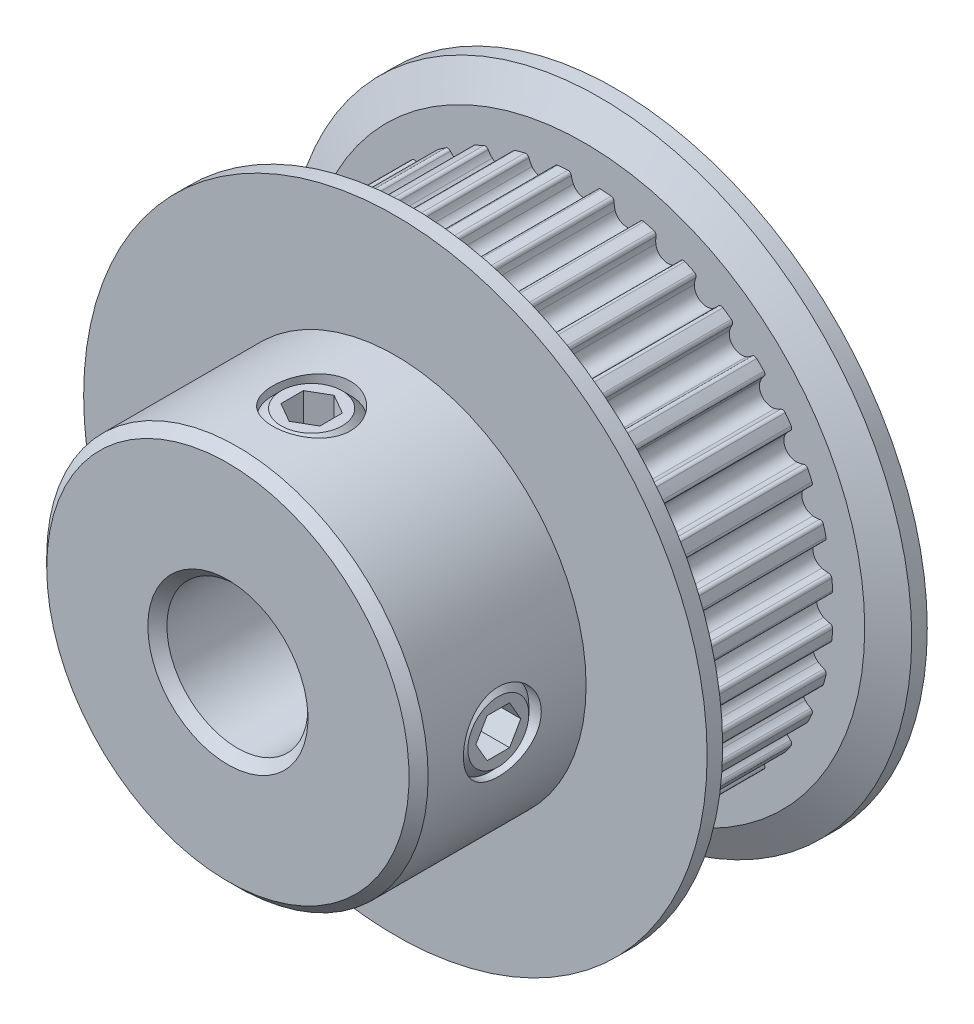
SolidWorks part; units mm, degrees
ref_plane "Front Plane" through (0, 0, 0) normal (0, 0, 1) x (1, 0, 0)
ref_plane "Top Plane" through (0, 0, 0) normal (0, 1, 0) x (1, 0, 0)
ref_plane "Right Plane" through (0, 0, 0) normal (1, 0, 0) x (0, 0, -1)
sketch "Sketch1" plane through (0, 0, 0) normal (0, 0, 1) x (1, 0, 0)
  line L1 (-1.8459, 10.4515) -> (1.8459, 10.4515) construction
  line L4 (0, 0) -> (0, 10.4515) construction
  line L5 (0, 10.4515) -> (0, 14.6063) construction
  line L6 (0, 11.4555) -> (1.9924, 11.2809) construction
  line L7 (1.9924, 11.2809) -> (2.8218, 11.1344) construction
  line L8 (1.9924, 11.2809) -> (1.8459, 10.4515) construction
  line L9 (-1.9924, 11.2809) -> (-1.8459, 10.4515) construction
  line L10 (-1.9482, 11.0308) -> (-2.4785, 14.0335)
  line L11 (-2.4785, 14.0335) -> (2.4785, 14.0335)
  line L12 (2.4785, 14.0335) -> (1.9482, 11.0308)
  circle A0 centre (0, 0) radius 11.4555 construction
  circle A1 centre (0, 0) radius 14.0335 construction
  circle A2 centre (0, 0) radius 11.2015 construction
  arc A3 (-0.4989, 10.7633) -> (0.4989, 10.7633) centre (0, 11.0065) ccw
  arc A4 (-0.4989, 10.7633) -> (-0.5884, 11.0497) centre (0.4, 11.2015) cw
  arc A5 (-1.9482, 11.0308) -> (-0.7467, 11.1766) centre (0, 0) cw
  arc A6 (-0.5884, 11.0497) -> (-0.7467, 11.1766) centre (-0.7367, 11.0269) ccw
  arc A7 (1.9482, 11.0308) -> (0.7467, 11.1766) centre (0, 0) ccw
  arc A8 (0.5884, 11.0497) -> (0.7467, 11.1766) centre (0.7367, 11.0269) cw
  arc A9 (0.4989, 10.7633) -> (0.5884, 11.0497) centre (-0.4, 11.2015) ccw
  point P6 (0, 20.9083)
  point P11 (0, 11.4555)
  point P13 (0, 14.0335)
  point P14 (0, 11.2015)
  dimension "D1" = 6.302
  dimension "D2" = 3.1508
sketch "Sketch2" plane through (0, 0, 0) normal (1, 0, 0) x (0, 0, -1)
  line L0 (-8.7249, 3.175) -> (8.7249, 3.175)
  line L1 (-8.7249, 3.175) -> (-8.7249, 8.585)
  line L2 (-8.7249, 8.585) -> (-1.1851, 8.585)
  line L3 (-1.1851, 8.585) -> (-1.1851, 14.0335)
  line L4 (-1.1851, 14.0335) -> (0.2149, 14.0335) construction
  line L5 (0.2149, 14.0335) -> (0.2149, 11.2015) construction
  line L6 (0.2149, 11.2015) -> (7.3249, 11.2015)
  line L7 (7.3249, 11.2015) -> (7.3249, 14.0335) construction
  line L8 (7.3249, 14.0335) -> (8.7249, 14.0335) construction
  line L9 (8.7249, 14.0335) -> (8.7249, 3.175)
  line L10 (-8.7249, 0) -> (8.7249, 0) construction
  line L11 (8.0249, 14.0335) -> (7.3249, 12.6175)
  line L12 (0.2149, 12.6175) -> (-0.4851, 14.0335)
  line L13 (-1.1851, 14.0335) -> (-0.4851, 14.0335)
  line L14 (0.2149, 12.6175) -> (0.2149, 11.2015)
  line L15 (7.3249, 11.2015) -> (7.3249, 12.6175)
  line L16 (8.0249, 14.0335) -> (8.7249, 14.0335)
  arc A0 (0.2149, 12.6175) -> (-0.4851, 14.0335) centre (-1.5673, 12.6175) ccw construction
  arc A1 (7.3249, 12.6175) -> (8.0249, 14.0335) centre (9.1071, 12.6175) cw construction
  point P12 (0.2149, 12.6175)
  point P14 (-0.4851, 14.0335)
  point P20 (7.3249, 12.6175)
  point P21 (8.0249, 14.0335)
  point P25 (7.3249, 0)
  point P26 (0.2149, 0)
revolve "Revolve1" add sketch "Sketch2" angle 360 mid plane about L10
sketch "Sketch3" plane through (0, 0, 0) normal (0, 0, 1) x (1, 0, 0)
  line L6 (2.4785, 14.0335) -> (-2.4785, 14.0335)
  line L7 (1.9482, 11.0308) -> (2.4785, 14.0335)
  line L8 (-2.4785, 14.0335) -> (-1.9482, 11.0308)
  line L9 (2.4785, 14.0335) -> (-2.4785, 14.0335)
  line L10 (1.9482, 11.0308) -> (2.4785, 14.0335)
  line L11 (-2.4785, 14.0335) -> (-1.9482, 11.0308)
  arc A8 (1.9482, 11.0308) -> (0.7467, 11.1766) centre (0, 0) ccw
  arc A9 (0.7467, 11.1766) -> (0.5884, 11.0497) centre (0.7367, 11.0269) ccw
  arc A10 (0.4989, 10.7633) -> (0.5884, 11.0497) centre (-0.4, 11.2015) ccw
  arc A11 (-0.4989, 10.7633) -> (0.4989, 10.7633) centre (0, 11.0065) ccw
  arc A12 (-0.5884, 11.0497) -> (-0.4989, 10.7633) centre (0.4, 11.2015) ccw
  arc A13 (-0.5884, 11.0497) -> (-0.7467, 11.1766) centre (-0.7367, 11.0269) ccw
  arc A14 (-0.7467, 11.1766) -> (-1.9482, 11.0308) centre (0, 0) ccw
  arc A15 (1.9482, 11.0308) -> (0.7467, 11.1766) centre (0, 0) ccw
  arc A16 (0.7467, 11.1766) -> (0.5884, 11.0497) centre (0.7367, 11.0269) ccw
  arc A17 (0.4989, 10.7633) -> (0.5884, 11.0497) centre (-0.4, 11.2015) ccw
  arc A18 (-0.4989, 10.7633) -> (0.4989, 10.7633) centre (0, 11.0065) ccw
  arc A19 (-0.5884, 11.0497) -> (-0.4989, 10.7633) centre (0.4, 11.2015) ccw
  arc A20 (-0.5884, 11.0497) -> (-0.7467, 11.1766) centre (-0.7367, 11.0269) ccw
  arc A21 (-0.7467, 11.1766) -> (-1.9482, 11.0308) centre (0, 0) ccw
  dimension "D1" = 0
extrude "Cut-Extrude1" cut sketch "Sketch3" against normal up to vertex (7.3249 mm away) from vertex up to point (0, 11.2015, -7.3249) starting at point (0, 11.2015, -0.2149)
pattern_circular "CirPattern1" count 36 over 360 about axis through (0, 0, 8.7249) along (0, 0, 1) of "Cut-Extrude1"
sketch "Sketch4" plane through (0, 0, 0) normal (1, 0, 0) x (0, -1, 0)
  line L0 (0, -1.1851) -> (0, -8.7249) construction
  line L1 (-8.585, -1.1851) -> (8.585, -1.1851) construction
  line L2 (-8.585, -8.7249) -> (8.585, -8.7249) construction
  circle A0 centre (0, -4.955) radius 1.7526
extrude "Cut-Extrude2" cut sketch "Sketch4" along normal through all
ref_plane "Plane1" through (0, 0, 4.955) normal (0, 0, 1) x (1, 0, 0)
sketch "Sketch5" plane through (0, 0, 4.955) normal (0, 0, 1) x (1, 0, 0)
  line L0 (0, 0.1664) -> (0, 8.585) construction
  line L1 (3.175, -1.3716) -> (3.175, 0)
  line L2 (3.556, -1.7526) -> (8.0232, -1.7526)
  line L3 (3.175, 0) -> (8.585, 0) construction
  line L4 (3.175, 0) -> (8.4042, 0)
  line L5 (8.4042, 0) -> (8.4042, -1.3716)
  line L6 (3.556, -1.7526) -> (3.175, -1.3716)
  line L7 (8.4042, -1.3716) -> (8.0232, -1.7526)
  circle A0 centre (0, 0) radius 8.585 construction
  circle A1 centre (0, 0) radius 3.175 construction
  point P2 (3.175, -1.7526)
  point P11 (8.4042, -1.7526)
revolve "Revolve2" add sketch "Sketch5" angle 360 mid plane about L4
sketch "Sketch6" plane through (8.4042, 5.3841, 0) normal (-1, 0, 0) x (0, -1, 0)
  line L1 (5.3841, 5.9669) -> (4.5078, 5.4609)
  line L2 (4.5078, 5.4609) -> (4.5078, 4.4491)
  line L3 (4.5078, 4.4491) -> (5.3841, 3.9431)
  line L4 (5.3841, 3.9431) -> (6.2604, 4.4491)
  line L5 (6.2604, 4.4491) -> (6.2604, 5.4609)
  line L6 (6.2604, 5.4609) -> (5.3841, 5.9669)
  circle A0 centre (5.3841, 4.955) radius 0.8763 construction
  dimension "D1" = 1.7526
extrude "Cut-Extrude3" cut sketch "Sketch6" along normal blind 1.3144
pattern_circular "CirPattern2" count 2 over 90 about axis through (0, 0, 8.7249) along (0, 0, 1) of "Cut-Extrude2", "Revolve2", "Cut-Extrude3"
chamfer "Chamfer1" distance 0.4293 angle 45 2 edges at (3.175, 0, 8.7249) (8.585, 0, 8.7249)
ref_axis "Center Axis 1" through (0, 0, -8.7249) along (0, 0, 1)
ref_plane "Contact Plane 1" through (0, 0, 8.7249) normal (0, 0, 1) x (1, 0, 0)
ref_plane "Contact Plane 2" through (0, 0, -8.7249) normal (0, 0, -1) x (-1, 0, 0)
equation "\"D2@Sketch1\" = \"D1@Sketch1\"/2"
equation "\"D1@Sketch6\" = \"Set Screw@Sketch4\" / 2"
equation "\"D1@Cut-Extrude3\" = \"D1@Sketch6\"*.75"
equation "\"D1@Chamfer1\"=\"Hub Dia@Sketch2\"*.025"
